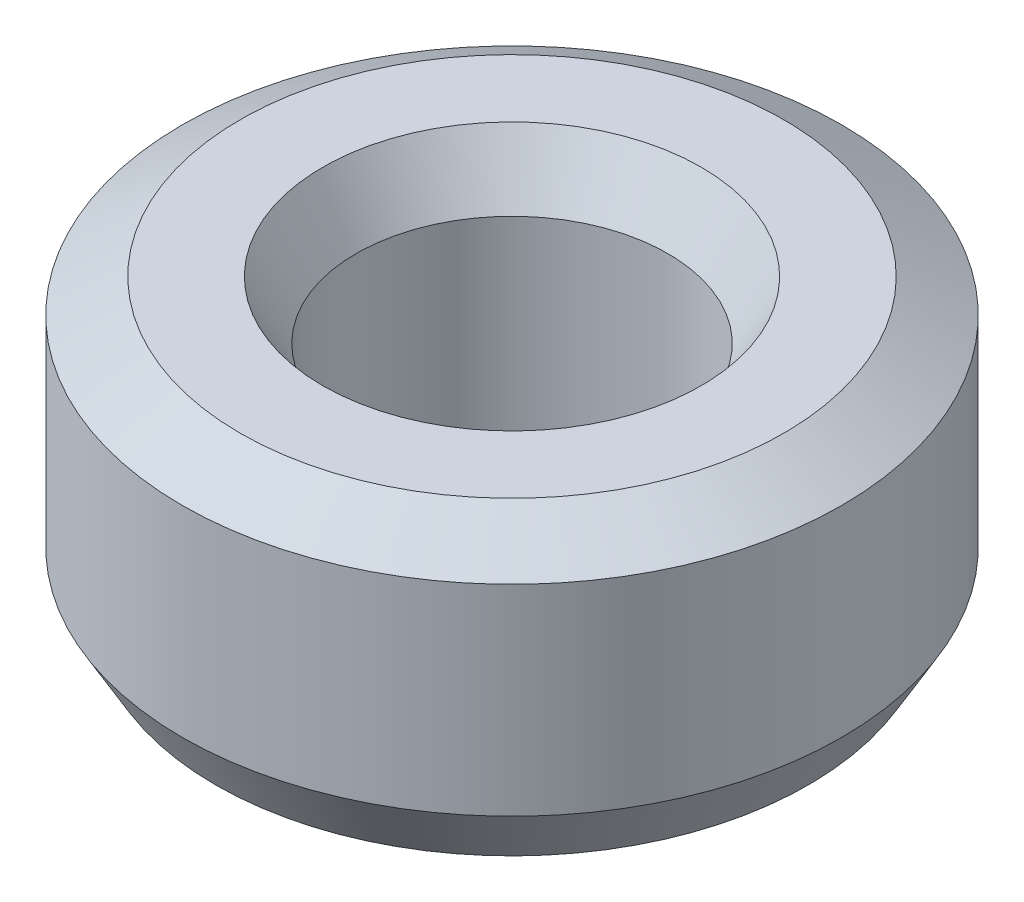
SolidWorks part; units mm, degrees
ref_plane "Front Plane" through (0, 0, 0) normal (0, 0, 1) x (1, 0, 0)
ref_plane "Top Plane" through (0, 0, 0) normal (0, 1, 0) x (1, 0, 0)
ref_plane "Right Plane" through (0, 0, 0) normal (1, 0, 0) x (0, 0, -1)
sketch "Sketch1" plane through (0, 0, 0) normal (0, 1, 0) x (1, 0, 0)
  circle A0 centre (0, 0) radius 12.5
  dimension "SLEEVE_OD" = 25
extrude "Boss-Extrude1" add sketch "Sketch1" along normal blind 11.0856
sketch "Sketch2" plane through (0, 0, 0) normal (0, 1, 0) x (1, 0, 0)
  circle A0 centre (0, 0) radius 5.906
  dimension "BORE_D" = 11.8121
extrude "Cut-Extrude1" cut sketch "Sketch2" along normal through all
chamfer "Chamfer1" distance 1.2697 angle 60 4 edges at (0, 11.0856, 5.906) (0, 0, 5.906) (0, 0, 12.5) (0, 11.0856, 12.5) first distance on face at (0, 11.0856, 5.906) first distance on face at (0, 0, 5.906) first distance on face at (0, 11.0856, 12.5)
